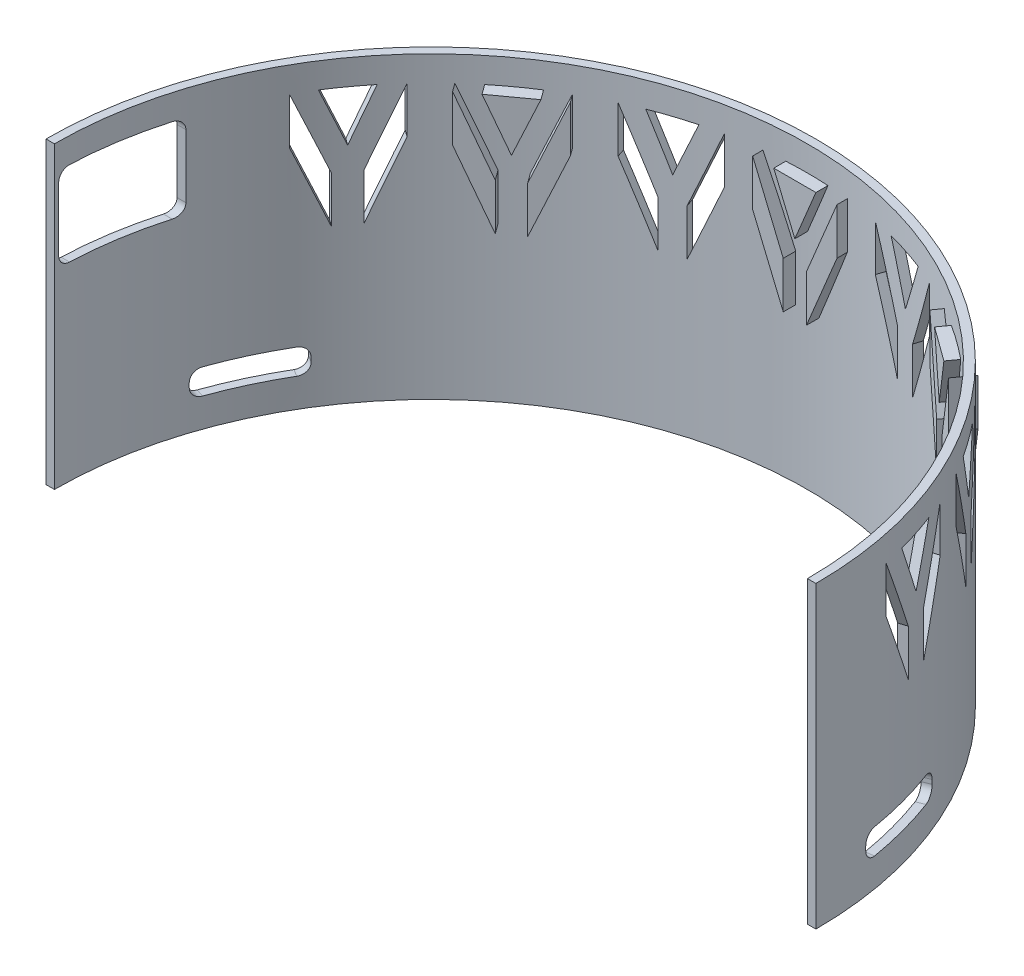
SolidWorks part; units mm, degrees
ref_plane "Front Plane" through (0, 0, 0) normal (0, 0, 1) x (1, 0, 0)
ref_plane "Top Plane" through (0, 0, 0) normal (0, 1, 0) x (1, 0, 0)
ref_plane "Right Plane" through (0, 0, 0) normal (1, 0, 0) x (0, 0, -1)
sketch "Sketch1" plane through (0, 0, 0) normal (0, 1, 0) x (1, 0, 0)
  line L0 (0, 124.168) -> (0, -125.7458) construction
  line L1 (-136.0011, 0) -> (148.623, 0) construction
  line L2 (-48.4715, -75) -> (48.4715, -75)
  line L3 (-49.058, -77) -> (49.058, -77)
  arc A0 (48.4715, -75) -> (-48.4715, -75) centre (0, 0) ccw
  arc A1 (49.058, -77) -> (-49.058, -77) centre (0, 0) ccw
  dimension "D1" = 178.6
  dimension "D3" = 182.6
  dimension "D2" = 75
  dimension "D4" = 77
extrude "Boss-Extrude1" add sketch "Sketch1" along normal blind 71
ref_axis "Axis1" through (0, 71, 0) along (0, -1, 0)
fillet "Fillet1" radius 10 2 edges at (-49.058, 35.5, 77) (49.058, 35.5, 77)
sketch "Sketch2" plane through (0, 0, 77) normal (0, 0, 1) x (1, 0, 0)
  line L0 (0, 94.4811) -> (0, -36.6428) construction
  line L1 (46.051, 0) -> (51.7153, 0) construction
  line L2 (-48, 16) -> (48, 16)
  line L4 (-48, 16) -> (-48, 0)
  line L5 (-48, 0) -> (48, 0)
  line L6 (48, 16) -> (48, 0)
  line L7 (-48, 16) -> (48, 0) construction
  line L8 (-48, 0) -> (48, 16) construction
  line L9 (-46.051, 71) -> (46.051, 71) construction
  point P3 (0, 8)
  dimension "D1" = 55
  dimension "D2" = 96
extrude "Cut-Extrude1" cut sketch "Sketch2" against normal blind 5
sketch "Sketch3" plane through (0, 0, 77) normal (0, 0, 1) x (1, 0, 0)
  line L0 (0, 94.4811) -> (0, -26.607) construction
  line L1 (46.051, 16) -> (-46.051, 16) construction
  line L2 (-23.5, 16) -> (-1.5, 16)
  line L3 (-23.5, 16) -> (-23.5, 23.5)
  line L4 (-23.5, 23.5) -> (-1.5, 23.5)
  line L5 (-1.5, 16) -> (-1.5, 23.5)
  dimension "D1" = 22
  dimension "D2" = 7.5
  dimension "D3" = 1.5
extrude "Cut-Extrude2" cut sketch "Sketch3" against normal blind 5
fillet "Fillet2" radius 5 4 edges at (-48, 16, 75.9041) (-48, 0, 75.9041) (48, 16, 75.9041) (48, 0, 75.9041)
fillet "Fillet3" radius 2 4 edges at (-1.5, 16, 76) (-1.5, 23.5, 76) (-23.5, 16, 76) (-23.5, 23.5, 76)
sketch "Sketch4" plane through (0, 0, 0) normal (0, 0, 1) x (1, 0, 0)
  line L0 (0, 103.2008) -> (0, -37.4655) construction
  line L1 (-5, 65) -> (5, 65)
  line L2 (-5, 65) -> (0, 53)
  line L3 (0, 53) -> (5, 65)
  line L8 (-46.051, 71) -> (46.051, 71) construction
  line L9 (-10, 65) -> (-2.75, 47.6)
  line L10 (-2.75, 47.6) -> (-2.75, 36.6)
  line L11 (-2.75, 36.6) -> (-10, 54)
  line L12 (-10, 54) -> (-10, 65)
  line L13 (10, 65) -> (2.75, 47.6)
  line L14 (2.75, 47.6) -> (2.75, 36.6)
  line L15 (2.75, 36.6) -> (10, 54)
  line L16 (10, 54) -> (10, 65)
  point P6 (0, 65)
  dimension "D1" = 10
  dimension "D2" = 6
  dimension "D3" = 5
  dimension "D4" = 11
  dimension "D5" = 12
  dimension "D6" = 2.75
extrude "Cut-Extrude3" cut sketch "Sketch4" against normal blind 132
ref_plane "Plane1" through (0, 0, 0) normal (0.2588, 0, 0.9659) x (0, -1, 0)
sketch "Sketch6" plane through (0, 0, 0) normal (0.2588, 0, 0.9659) x (0, -1, 0)
  line L0 (-71, 0) -> (0, 0) construction
  line L1 (-6.8, 0) -> (-12.8, 0)
  line L2 (-6.8, 0) -> (-6.8, 100)
  line L3 (-6.8, 100) -> (-12.8, 100)
  line L4 (-12.8, 0) -> (-12.8, 100)
  line L5 (0, -91.3) -> (0, 91.3) construction
  dimension "D1" = 100
  dimension "D2" = 6
  dimension "D3" = 6.8
revolve "Cut-Revolve1" cut sketch "Sketch6" angle 14 mid plane about axis through (0, 71, 0) along (0, -1, 0)
pattern_circular "CirPattern1" count 2 over 140 about axis through (0, 0, 0) along (0, 1, 0) of "Cut-Revolve1"
sketch "Sketch7" plane through (0, 0, 0) normal (1, 0, 0) x (0, 0, -1)
  line L0 (0, 71) -> (0, 0) construction
  line L1 (1, 65) -> (27, 65)
  line L2 (1, 65) -> (1, 45)
  line L3 (1, 45) -> (27, 45)
  line L4 (27, 65) -> (27, 45)
  line L5 (89.3, 71) -> (-75, 71) construction
  dimension "D1" = 1
  dimension "D2" = 26
  dimension "D3" = 6
  dimension "D4" = 20
extrude "Cut-Extrude4" cut sketch "Sketch7" against normal blind 122
fillet "Fillet4" radius 2.5 12 edges at (83.7247, 12.8, -33.827) (89.4212, 12.8, -12.5673) (89.4212, 6.8, -12.5673) (83.7247, 6.8, -33.827) (-85.8804, 12.8, -27.9042) (-85.8804, 6.8, -27.9042) (-76.5787, 12.8, -47.8517) (-76.5787, 6.8, -47.8517) (-90.2945, 65, -1) (-90.2945, 45, -1) (-86.1684, 45, -27) (-86.1684, 65, -27)
pattern_circular "CirPattern2" count 20 over 360 about axis through (0, 71, 0) along (0, 1, 0) skipping 4, 5, 6, 7, 8, 9, 10, 11, 12, 13, 14, 15 of "Cut-Extrude3"
sketch "Sketch8" plane through (0, 0, 0) normal (0, 1, 0) x (1, 0, 0)
  line L5 (116.5647, -77) -> (-113.2287, -77)
  line L6 (116.5647, -77) -> (116.5647, 0)
  line L7 (116.5647, 0) -> (-113.2287, 0)
  line L8 (-113.2287, -77) -> (-113.2287, 0)
  dimension "D1" = 77
extrude "Cut-Extrude6" cut sketch "Sketch8" along normal blind 80
ref_plane "Plane2" through (0, 0, -91.3) normal (0, 0, -1) x (-1, 0, 0)
sketch "Sketch10" plane through (0, 0, -91.3) normal (0, 0, -1) x (-1, 0, 0)
  line L0 (-5, 65) -> (5, 65)
  line L1 (5, 65) -> (0, 53)
  line L2 (0, 53) -> (-5, 65)
  line L3 (-10, 65) -> (-2.75, 47.6)
  line L4 (-2.75, 47.6) -> (-2.75, 36.6)
  line L5 (-2.75, 36.6) -> (-10, 54)
  line L6 (-10, 54) -> (-10, 65)
  line L7 (10, 65) -> (10, 54)
  line L8 (10, 54) -> (2.75, 36.6)
  line L9 (2.75, 36.6) -> (2.75, 47.6)
  line L10 (2.75, 47.6) -> (10, 65)
extrude "Boss-Extrude2" add sketch "Sketch10" against normal blind 5
ref_plane "Plane3" through (53.6648, 0, -73.8633) normal (0.5878, 0, -0.809) x (0, -1, 0)
sketch "Sketch11" plane through (53.6648, 0, -73.8633) normal (0.5878, 0, -0.809) x (0, -1, 0)
  line L0 (-65, -5) -> (-65, 5)
  line L1 (-65, 5) -> (-53, 0)
  line L2 (-53, 0) -> (-65, -5)
  line L3 (-65, -10) -> (-47.6, -2.75)
  line L4 (-47.6, -2.75) -> (-36.6, -2.75)
  line L5 (-36.6, -2.75) -> (-54, -10)
  line L6 (-54, -10) -> (-65, -10)
  line L7 (-65, 10) -> (-54, 10)
  line L8 (-54, 10) -> (-36.6, 2.75)
  line L9 (-36.6, 2.75) -> (-47.6, 2.75)
  line L10 (-47.6, 2.75) -> (-65, 10)
extrude "Boss-Extrude3" add sketch "Sketch11" against normal blind 5
ref_plane "Plane4" through (-53.6648, 0, -73.8633) normal (-0.5878, 0, -0.809) x (0, -1, 0)
sketch "Sketch12" plane through (-53.6648, 0, -73.8633) normal (-0.5878, 0, -0.809) x (0, -1, 0)
  line L0 (-65, 5) -> (-53, 0)
  line L1 (-53, 0) -> (-65, -5)
  line L2 (-65, -5) -> (-65, 5)
  line L3 (-65, 10) -> (-54, 10)
  line L4 (-54, 10) -> (-36.6, 2.75)
  line L5 (-36.6, 2.75) -> (-47.6, 2.75)
  line L6 (-47.6, 2.75) -> (-65, 10)
  line L7 (-65, -10) -> (-47.6, -2.75)
  line L8 (-47.6, -2.75) -> (-36.6, -2.75)
  line L9 (-36.6, -2.75) -> (-54, -10)
  line L10 (-54, -10) -> (-65, -10)
extrude "Boss-Extrude4" add sketch "Sketch12" against normal blind 5
equation "\"D5@Sketch4\"=20-\"D2@Sketch4\"-2"
